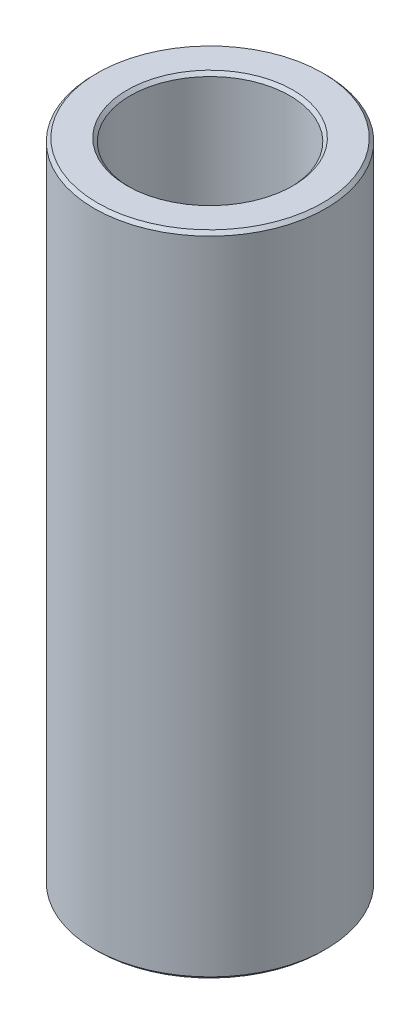
SolidWorks part; units mm, degrees
ref_plane "Front Plane" through (0, 0, 0) normal (0, 0, 1) x (1, 0, 0)
ref_plane "Top Plane" through (0, 0, 0) normal (0, 1, 0) x (1, 0, 0)
ref_plane "Right Plane" through (0, 0, 0) normal (1, 0, 0) x (0, 0, -1)
sketch "Sketch1" plane through (0, 0, 0) normal (0, 1, 0) x (1, 0, 0)
  circle A0 centre (0, 0) radius 45
  dimension "SLEEVE_OD" = 90
extrude "Boss-Extrude1" add sketch "Sketch1" along normal blind 251.7291
sketch "Sketch2" plane through (0, 0, 0) normal (0, 1, 0) x (1, 0, 0)
  circle A0 centre (0, 0) radius 30.9851
  dimension "BORE_D" = 61.9702
extrude "Cut-Extrude1" cut sketch "Sketch2" along normal through all
chamfer "Chamfer1" distance 1.2551 angle 45 4 edges at (0, 251.7291, 30.9851) (0, 0, 30.9851) (0, 0, 45) (0, 251.7291, 45)
